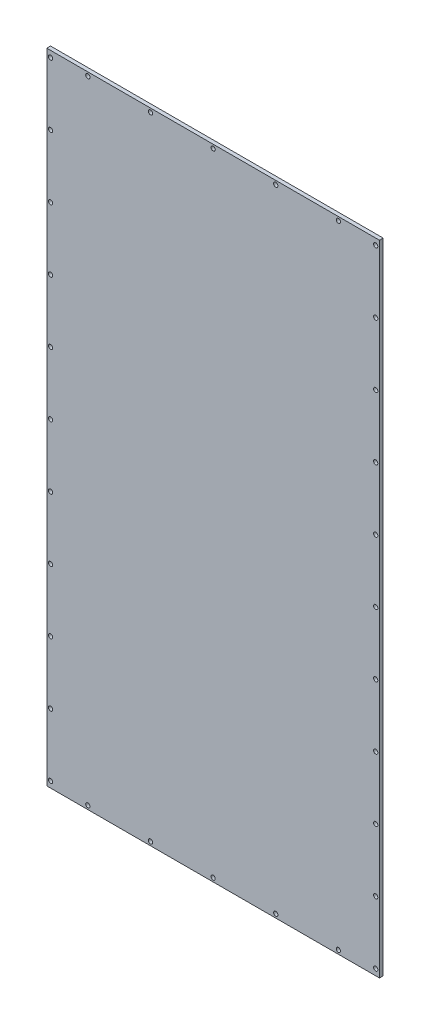
SolidWorks part; units mm, degrees
ref_plane "Front" through (0, 0, 0) normal (0, 0, 1) x (1, 0, 0)
ref_plane "Top" through (0, 0, 0) normal (0, 1, 0) x (1, 0, 0)
ref_plane "Right" through (0, 0, 0) normal (1, 0, 0) x (0, 0, -1)
sketch "Sketch1" plane through (0, 0, 0) normal (0, 0, 1) x (1, 0, 0)
  line L1 (0, 0) -> (265.54, 0)
  line L2 (0, 0) -> (0, 510)
  line L3 (0, 510) -> (265.54, 510)
  line L4 (265.54, 0) -> (265.54, 510)
  dimension "D1" = 510
  dimension "D2" = 265.54
extrude "Boss-Extrude1" add sketch "Sketch1" along normal blind 2.9972
hole_wizard "M3 Clearance Hole1" positions "Sketch3" profile "Sketch2" hole size "M3" standard "ANSI Metric" end condition through all
sketch "Sketch3" plane through (0, 0, 2.9972) normal (0, 0, 1) x (1, 0, 0)
  line L0 (262.54, 0) -> (262.54, 510) construction
  line L1 (0, 0) -> (265.54, 0) construction
  line L2 (265.54, 510) -> (0, 510) construction
  line L3 (262.54, 510) -> (265.54, 507) construction
  line L4 (265.54, 0) -> (265.54, 510) construction
  line L5 (265.54, 507) -> (0, 507) construction
  line L6 (0, 510) -> (0, 0) construction
  point P22 (262.54, 255)
  dimension "D1" = 3
  dimension "D2" = 3
sketch "Sketch2" plane through (262.54, 255, 2.9972) normal (1, 0, 0) x (0, -1, 0)
  line L0 (0, 0) -> (0, 2.9972)
  line L1 (0, 2.9972) -> (1.7, 2.9972)
  line L2 (1.7, 2.9972) -> (1.7, 0)
  line L5 (1.7, 0) -> (0, 0)
  line L11 (0, -6.35) -> (0, 107.95) construction
  dimension "Thru Hole Dia." = 3.4
  dimension "Thru Hole Depth" = 2.9972
hole_wizard "M3 Clearance Hole2" positions "Sketch4" profile "Sketch5" hole size "M3" standard "ANSI Metric" end condition through all
sketch "Sketch4" plane through (0, 0, 2.9972) normal (0, 0, 1) x (1, 0, 0)
  line L0 (262.5428, 510) -> (262.5428, 0) construction
  line L1 (265.54, 510) -> (0, 510) construction
  line L2 (0, 0) -> (265.54, 0) construction
  line L4 (265.54, 3) -> (0, 3) construction
  line L5 (265.54, 0) -> (265.54, 510) construction
  line L6 (0, 510) -> (0, 0) construction
  line L8 (3, 0) -> (3, 510) construction
  line L10 (265.54, 507) -> (0, 507) construction
  point P27 (132.77, 507)
  point P31 (0, 0)
  dimension "D1" = 2.9972
  dimension "D2" = 3
  dimension "D3" = 3
  dimension "D4" = 3
sketch "Sketch5" plane through (132.77, 507, 2.9972) normal (1, 0, 0) x (0, -1, 0)
  line L0 (0, 0) -> (0, 2.9972)
  line L1 (0, 2.9972) -> (1.7, 2.9972)
  line L2 (1.7, 2.9972) -> (1.7, 0)
  line L5 (1.7, 0) -> (0, 0)
  line L11 (0, -6.35) -> (0, 107.95) construction
  dimension "Thru Hole Dia." = 3.4
  dimension "Thru Hole Depth" = 2.9972
pattern_linear "LPattern1" count 6 spacing 50 along (0, -1, 0) count 6 spacing 50 along (0, 1, 0) of "M3 Clearance Hole1" pattern seed only yes
pattern_linear "LPattern2" count 3 spacing 50 along (1, 0, 0) count 3 spacing 50 along (-1, 0, 0) of "M3 Clearance Hole2" pattern seed only yes
ref_plane "Plane1" through (132.77, 0, 0) normal (-1, 0, 0) x (0, 0, 1)
ref_plane "Plane2" through (0, 255, 0) normal (0, 1, 0) x (1, 0, 0)
mirror "Mirror1" about plane through (132.77, 0, 0) normal (-1, 0, 0) of "LPattern1", "M3 Clearance Hole1"
mirror "Mirror2" about plane through (0, 255, 0) normal (0, 1, 0) of "LPattern2", "M3 Clearance Hole2"
